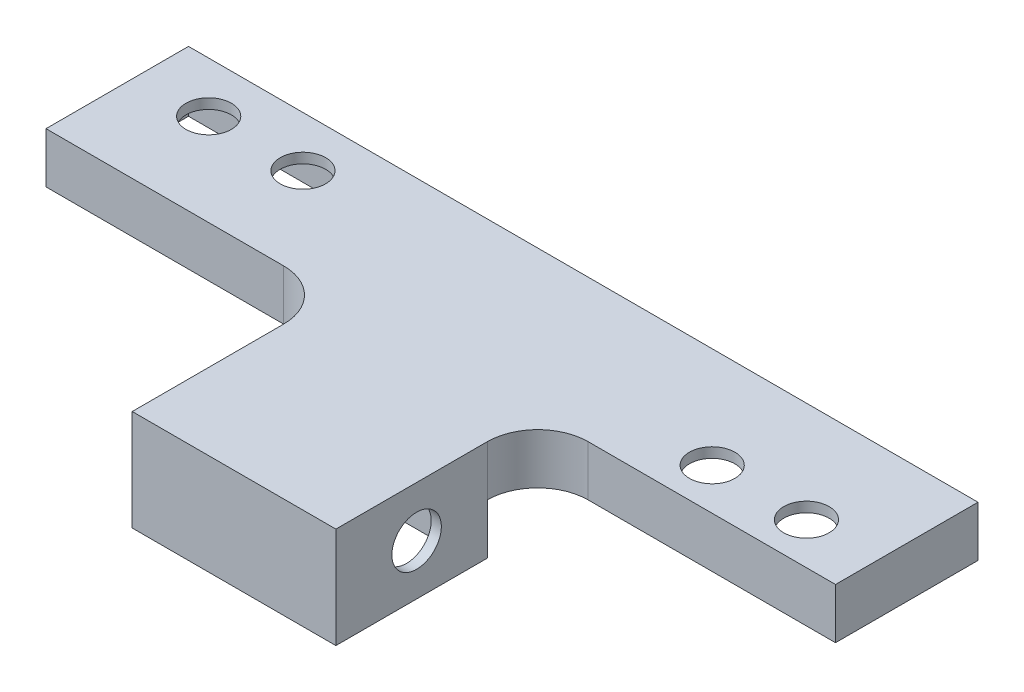
SolidWorks part; units mm, degrees
ref_plane "Front Plane" through (0, 0, 0) normal (0, 0, 1) x (1, 0, 0)
ref_plane "Top Plane" through (0, 0, 0) normal (0, 1, 0) x (1, 0, 0)
ref_plane "Right Plane" through (0, 0, 0) normal (1, 0, 0) x (0, 0, -1)
sketch "Sketch2" plane through (0, 0, 0) normal (0, 1, 0) x (1, 0, 0)
  line L5 (-39.115, 0.8806) -> (-39.115, 10)
  line L6 (-39.115, 10) -> (39.115, 10)
  line L9 (-39.115, 0.8806) -> (-39.115, -4.1194)
  line L11 (39.115, 0.8806) -> (39.115, -4.1194)
  line L17 (39.115, 10) -> (39.115, 0.8806)
  line L18 (-43.0342, 0) -> (-32.115, 0) construction
  line L19 (-43.0342, 5) -> (-39.115, 5) construction
  line L20 (-32.115, 20.6942) -> (-32.115, 7.25) construction
  line L21 (32.115, 20.6942) -> (32.115, 10) construction
  line L22 (22.775, 20.6942) -> (22.775, 10) construction
  line L23 (-22.775, 20.6942) -> (-22.775, 10) construction
  line L24 (-39.115, -4.1194) -> (-15.57, -4.1194)
  line L26 (-22.775, -14.1194) -> (-22.775, -24.3628) construction
  line L28 (14.6082, -4.1194) -> (39.115, -4.1194)
  line L29 (-10.57, -9.1194) -> (-10.57, -24.1194)
  line L30 (-10.57, -24.1194) -> (9.6082, -24.1194)
  line L31 (9.6082, -24.1194) -> (9.6082, -9.1194)
  line L32 (-22.775, 0) -> (-22.775, -4.1194) construction
  line L33 (39.115, 5) -> (44.6066, 5) construction
  line L36 (-32.115, 0) -> (-32.115, -19.1194) construction
  line L40 (22.775, -4.1194) -> (22.775, -26.3745) construction
  line L41 (20.525, 0) -> (22.775, 0) construction
  line L43 (39.115, 0) -> (44.6066, 0) construction
  line L44 (32.115, -4.1194) -> (32.115, -21.5429) construction
  arc A8 (-15.57, -4.1194) -> (-10.57, -9.1194) centre (-15.57, -9.1194) cw
  arc A9 (14.6082, -4.1194) -> (9.6082, -9.1194) centre (14.6082, -9.1194) ccw
  point P0 (0, 0)
  dimension "D7" = 5
  dimension "D15" = 5
  dimension "D2" = 10
  dimension "D3" = 15
  dimension "D4" = 78.23
  dimension "D5" = 7
  dimension "D6" = 7
  dimension "D8" = 14.1194
  dimension "D9" = 20
extrude "Boss-Extrude1" add sketch "Sketch2" along normal blind 5
sketch "Sketch8" plane through (0, 0, 0) normal (0, -1, 0) x (1, 0, 0)
  line L1 (-10.57, 24.1194) -> (9.6082, 24.1194)
  line L2 (-10.57, 24.1194) -> (-10.57, 9.1194)
  line L3 (-10.57, 9.1194) -> (9.6082, 9.1194)
  line L4 (9.6082, 24.1194) -> (9.6082, 9.1194)
extrude "Boss-Extrude2" add sketch "Sketch8" along normal blind 5
shell "Shell4" thickness 1 removed face at (-0.4809, -5, 16.6194) removed face at (-0.2404, 0, 1.5806)
sketch "Sketch9" plane through (-10.57, 0, 0) normal (-1, 0, 0) x (0, 0, 1)
  line L0 (16.1194, 12.2359) -> (16.1194, -13.7943) construction
  line L1 (29.2327, 0) -> (7.4664, 0) construction
  line L2 (9.1194, 5) -> (24.1194, 5) construction
  line L3 (24.1194, 5) -> (24.1194, -5) construction
  circle A0 centre (16.1194, 0) radius 2.45
  dimension "D3" = 4.9
  dimension "D1" = 5
  dimension "D2" = 8
extrude "Cut-Extrude3" cut sketch "Sketch9" against normal through all
sketch "Sketch10" plane through (0, 5, 0) normal (0, 1, 0) x (1, 0, 0)
  line L0 (-51.7119, 5) -> (45.3103, 5) construction
  line L1 (39.115, 10) -> (-39.115, 10) construction
  line L2 (45.3103, 0) -> (-50.4648, 0) construction
  line L3 (-39.115, 10) -> (-39.115, -4.1194) construction
  line L4 (39.115, -4.1194) -> (39.115, 10) construction
  line L5 (-32.115, -17.6598) -> (-32.115, 21.5814) construction
  line L7 (-22.775, 21.5814) -> (-22.775, -27.0544) construction
  line L9 (22.775, -27.0544) -> (22.775, 18.1727) construction
  line L11 (32.115, 18.1727) -> (32.115, -27.0544) construction
  circle A0 centre (-32.115, 5) radius 2.25
  circle A1 centre (-22.775, 5) radius 2.25
  circle A2 centre (32.115, 0) radius 2.25
  circle A3 centre (22.775, 0) radius 2.25
  dimension "D7" = 4.5
  dimension "D8" = 4.5
  dimension "D9" = 4.5
  dimension "D10" = 4.5
  dimension "D1" = 5
  dimension "D2" = 10
  dimension "D3" = 7
  dimension "D4" = 9.34
  dimension "D5" = 7
  dimension "D6" = 9.34
extrude "Cut-Extrude4" cut sketch "Sketch10" against normal blind 10
